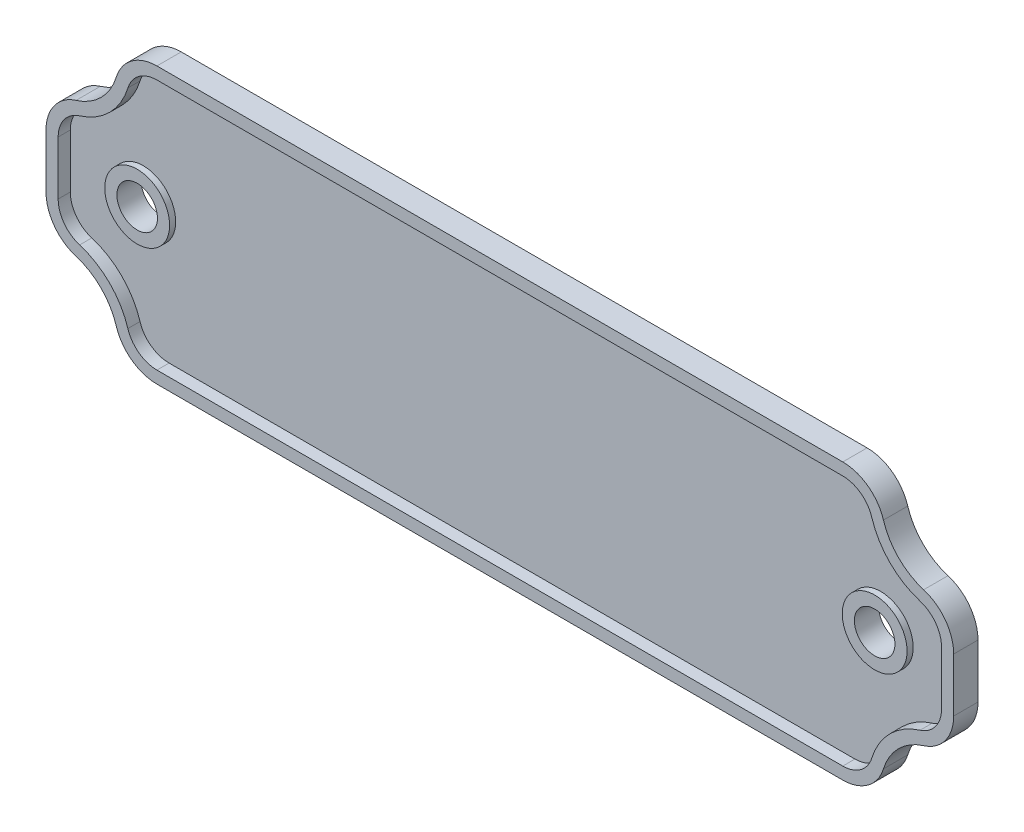
SolidWorks part; units mm, degrees
ref_plane "Front Plane" through (0, 0, 0) normal (0, 0, 1) x (1, 0, 0)
ref_plane "Top Plane" through (0, 0, 0) normal (0, 1, 0) x (1, 0, 0)
ref_plane "Right Plane" through (0, 0, 0) normal (1, 0, 0) x (0, 0, -1)
sketch "Sketch1" plane through (0, 0, 0) normal (0, 0, 1) x (1, 0, 0)
  line L0 (-79.3725, 0) -> (82.445, 0) construction
  line L1 (0, 44.8436) -> (0, -46.3067) construction
  line L2 (42.3139, 15.5) -> (-42.3139, 15.5)
  line L3 (-42.3139, 15.5) -> (-67.84, 15.5) construction
  line L4 (-54.5, 3.3139) -> (-54.5, 0)
  line L5 (-54.5, 3.3139) -> (-54.5, 27.9) construction
  line L6 (-54.5, -3.3139) -> (-54.5, 0)
  line L7 (-54.5, -3.3139) -> (-54.5, -27.9) construction
  line L8 (42.3139, -15.5) -> (-42.3139, -15.5)
  line L9 (54.5, -3.3139) -> (54.5, -27.9) construction
  line L10 (54.5, 3.3139) -> (54.5, 27.9) construction
  line L11 (42.3139, 15.5) -> (67.84, 15.5) construction
  line L12 (79.3725, 0) -> (-82.445, 0) construction
  line L13 (54.5, -3.3139) -> (54.5, 0)
  line L14 (54.5, 3.3139) -> (54.5, 0)
  line L15 (42.3139, 17) -> (-42.3139, 17)
  line L16 (-56, 3.3139) -> (-56, 0)
  line L17 (-56, -3.3139) -> (-56, 0)
  line L18 (42.3139, -17) -> (-42.3139, -17)
  line L19 (56, -3.3139) -> (56, 0)
  line L20 (56, 3.3139) -> (56, 0)
  circle A2 centre (-45.5, 0) radius 2.5
  circle A3 centre (-45.5, 0) radius 4
  arc A4 (-42.3139, 15.5) -> (-45.8981, 12.8529) centre (-42.3139, 11.75) ccw
  arc A5 (-45.8981, 12.8529) -> (-51.8529, 6.8981) centre (-54.5, 15.5) cw
  arc A6 (-51.8529, 6.8981) -> (-54.5, 3.3139) centre (-50.75, 3.3139) ccw
  arc A7 (-51.8529, -6.8981) -> (-54.5, -3.3139) centre (-50.75, -3.3139) cw
  arc A8 (-45.8981, -12.8529) -> (-51.8529, -6.8981) centre (-54.5, -15.5) ccw
  arc A9 (-42.3139, -15.5) -> (-45.8981, -12.8529) centre (-42.3139, -11.75) cw
  arc A10 (42.3139, -15.5) -> (45.8981, -12.8529) centre (42.3139, -11.75) ccw
  arc A11 (45.8981, -12.8529) -> (51.8529, -6.8981) centre (54.5, -15.5) cw
  arc A12 (51.8529, -6.8981) -> (54.5, -3.3139) centre (50.75, -3.3139) ccw
  arc A13 (51.8529, 6.8981) -> (54.5, 3.3139) centre (50.75, 3.3139) cw
  arc A14 (45.8981, 12.8529) -> (51.8529, 6.8981) centre (54.5, 15.5) ccw
  arc A15 (42.3139, 15.5) -> (45.8981, 12.8529) centre (42.3139, 11.75) cw
  circle A16 centre (45.5, 0) radius 4
  circle A17 centre (45.5, 0) radius 2.5
  arc A18 (-42.3139, 17) -> (-47.3317, 13.2941) centre (-42.3139, 11.75) ccw
  arc A19 (-47.3317, 13.2941) -> (-52.2941, 8.3317) centre (-54.5, 15.5) cw
  arc A20 (-52.2941, 8.3317) -> (-56, 3.3139) centre (-50.75, 3.3139) ccw
  arc A21 (-52.2941, -8.3317) -> (-56, -3.3139) centre (-50.75, -3.3139) cw
  arc A22 (-47.3317, -13.2941) -> (-52.2941, -8.3317) centre (-54.5, -15.5) ccw
  arc A23 (-42.3139, -17) -> (-47.3317, -13.2941) centre (-42.3139, -11.75) cw
  arc A24 (42.3139, -17) -> (47.3317, -13.2941) centre (42.3139, -11.75) ccw
  arc A25 (47.3317, -13.2941) -> (52.2941, -8.3317) centre (54.5, -15.5) cw
  arc A26 (52.2941, -8.3317) -> (56, -3.3139) centre (50.75, -3.3139) ccw
  arc A27 (52.2941, 8.3317) -> (56, 3.3139) centre (50.75, 3.3139) cw
  arc A28 (47.3317, 13.2941) -> (52.2941, 8.3317) centre (54.5, 15.5) ccw
  arc A29 (42.3139, 17) -> (47.3317, 13.2941) centre (42.3139, 11.75) cw
  point P10 (-54.5, 1.657)
  point P11 (-54.2113, 15.5)
  point P20 (-54.0715, 15.5)
  point P21 (-52.9924, 13.7446)
  point P22 (-54.1883, 15.2844)
  point P23 (-54.0136, 15.5)
  point P24 (-54.5, 15.5)
  point P26 (-54.5, 3.3139)
  point P27 (0, 0)
  point P59 (0, -15.5)
  point P60 (0, 15.5)
  dimension "D1" = 15.5
  dimension "D3" = 54.5
  dimension "D4" = 3.75
  dimension "D5" = 3.75
  dimension "D6" = 9
  dimension "D7" = 8
  dimension "D8" = 5
  dimension "D2" = 9
  dimension "D9" = 1.5
extrude "Boss-Extrude1" add sketch "Sketch1" along normal blind 1.5 contours A15 L2 A4 A5 A6 L4 L6 A7 A8 A9 L8 A10 A11 A12 L13 L14 A13 A14 A3 A16 region at (0, 0, 0)
extrude "Boss-Extrude2" add sketch "Sketch1<3>" along normal blind 3 contours A29 L15 A18 A19 A20 L16 L17 A21 A22 A23 L18 A24 A25 A26 L19 L20 A27 A28 L2 A15 A14 A13 L14 L13 A12 A11 A10 L8 A9 A8 A7 L6 L4 A6 A5 A4 region at (44.7375, 15.0316, 0)
sketch "Sketch1<3>" plane through (0, 0, 0) normal (0, 0, 1) x (1, 0, 0) same geometry as "Sketch1"
extrude "Boss-Extrude3" add sketch "Sketch1<4>" along normal blind 2.25 and the other way blind 0.75 contours A3 A2 | A16 A17 region at (-49.3869, 0, 0) region at (41.6131, 0, 0)
sketch "Sketch1<4>" plane through (0, 0, 0) normal (0, 0, 1) x (1, 0, 0) same geometry as "Sketch1"
